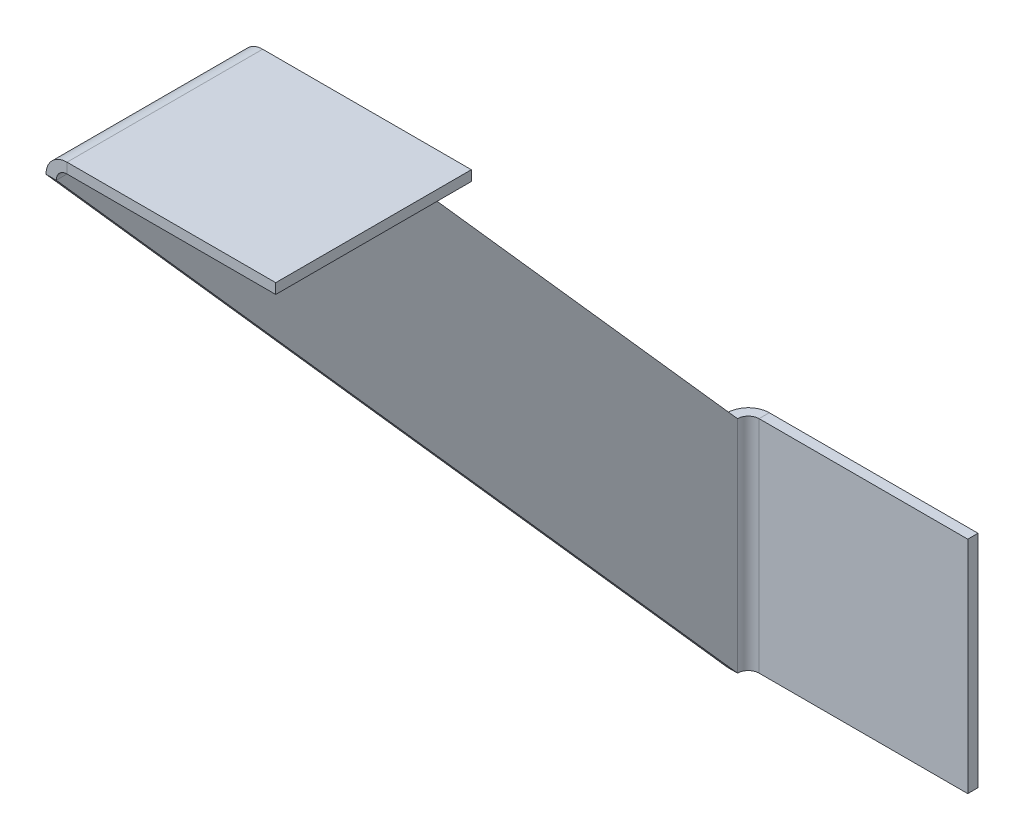
SolidWorks part; units mm, degrees
note: The reader was unsure of these and kept them because the rebuilt part matched: flange length of "Edge-Flange1".
ref_plane "Front Plane" through (0, 0, 0) normal (0, 0, 1) x (1, 0, 0)
ref_plane "Top Plane" through (0, 0, 0) normal (0, 1, 0) x (1, 0, 0)
ref_plane "Right Plane" through (0, 0, 0) normal (1, 0, 0) x (0, 0, -1)
sketch "Sketch1" plane through (0, 0, 0) normal (1, 0, 0) x (0, 0, -1)
  line L0 (0, 0) -> (-13.371, 0)
  line L1 (-13.371, 0) -> (33.1912, -52.4587)
  line L2 (33.1912, -52.4587) -> (33.1912, -37.3945)
  line L3 (33.1912, -37.3945) -> (0, 0)
  dimension "D1" = 10
  dimension "D2" = 50
sheet metal parameters "Sheet-Metal1" thickness 0.7 parameters "D1"=0.7366
base flange "Base-Flange1" sketch "Sketch1" thickness 0.7 reverse thickness direction no parameters "D1"=0.7366
edge flange "Edge-Flange1" sketch "Sketch8" flange profiles "Sketch8", "Sketch9" flange angle 90 flange length 15 flange position bend outside bend radius 0.7366 thickness 0.7 parameters "D6"=10, "D8"=1
sketch "Sketch8" plane through (0, 0, 0) normal (0, 1, 0) x (0, 0, 1)
  line L0 (0, 0) -> (13.371, 0) construction
  line L1 (0, 0) -> (13.371, 0)
  line L2 (0, 0) -> (0, 15)
  line L3 (0, 15) -> (13.371, 15)
  line L4 (13.371, 15) -> (13.371, 0)
sketch "Sketch9" plane through (0, 0, -33.1912) normal (0, 0, -1) x (0, 1, 0)
  line L0 (-52.4587, 0) -> (-37.3945, 0) construction
  line L1 (-52.4587, 0) -> (-37.3945, 0)
  line L2 (-52.4587, 0) -> (-52.4587, 15)
  line L3 (-52.4587, 15) -> (-37.3945, 15)
  line L4 (-37.3945, 15) -> (-37.3945, 0)
bend "EdgeBend1" bend radius 0.7366 bend angle 90 parameters "D5"=1
bend "EdgeBend2" bend radius 0.7366 bend angle 90 parameters "D5"=2
flat pattern "Flat-Pattern1" [suppressed]
sketch "Bend-Lines1" plane through (0, 0, 0) normal (0, 1, 0) x (1, 0, 0)
sketch3d "Bounding-Box1" [suppressed]
  line L0 (5.8921, 6.6382, 0) -> (-27.3936, -30.8627, 0) construction
  line L1 (13.371, 0, 0) -> (-19.9147, -37.5009, 0) construction
  line L2 (5.8921, 6.6382, 0) -> (13.371, 0, 0) construction
  line L3 (-27.3936, -30.8627, 0) -> (-19.9147, -37.5009, 0) construction
bend of the flat pattern "Flatten-<EdgeBend1>1"
bend of the flat pattern "Flatten-<EdgeBend2>1"
